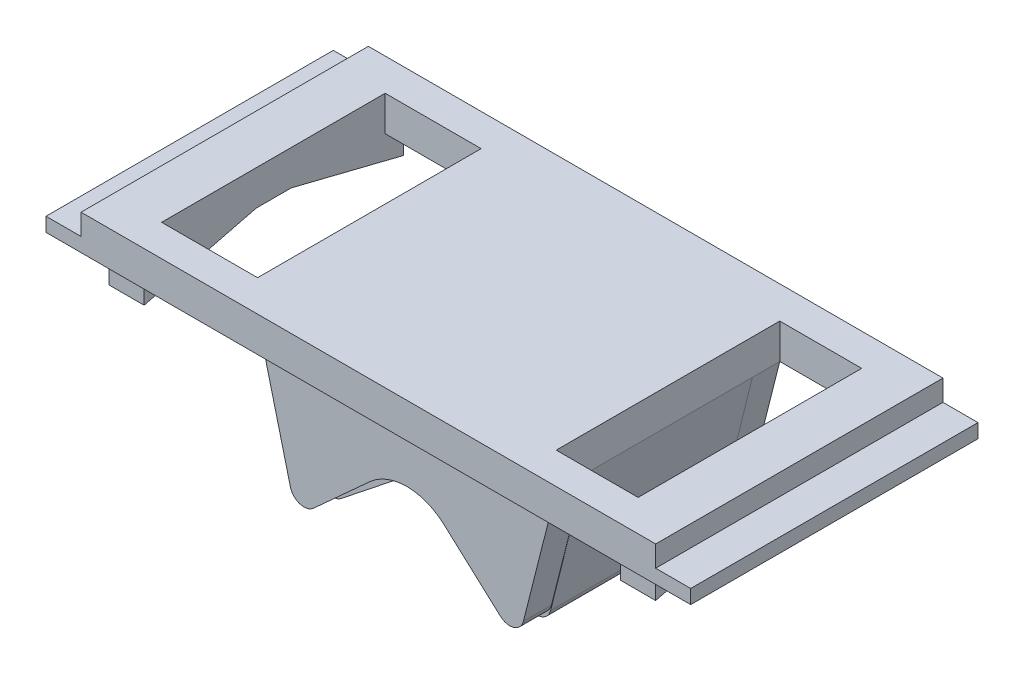
SolidWorks part; units mm, degrees
ref_plane "Спереди" through (0, 0, 0) normal (0, 0, 1) x (1, 0, 0)
ref_plane "Сверху" through (0, 0, 0) normal (0, 1, 0) x (1, 0, 0)
ref_plane "Справа" through (0, 0, 0) normal (1, 0, 0) x (0, 0, -1)
ref_plane "Плоскость4" through (0, 102.0014, 0) normal (0, 1, 0) x (1, 0, 0)
sketch "Эскиз1" plane through (0, 102.0014, 0) normal (0, 1, 0) x (1, 0, 0)
  line L0 (30.7418, -74.5527) -> (106.2994, -74.5527)
  line L1 (106.2994, -74.5527) -> (106.2994, -70.6514)
  line L2 (106.2994, -70.6514) -> (30.7418, -70.6514)
  line L3 (30.7418, -68.0527) -> (30.7418, -105.0527) construction
  line L4 (30.7418, -70.6514) -> (30.7418, -74.5527)
  line L5 (30.7418, -74.5527) -> (30.7418, -98.5527)
  line L6 (30.7418, -98.5527) -> (106.2994, -98.5527)
  line L7 (106.2994, -98.5527) -> (106.2994, -102.5527)
  line L8 (106.2994, -102.5527) -> (30.7418, -102.5527)
  line L9 (-55, -102.5527) -> (55, -102.5527) construction
  line L10 (30.7418, -98.5527) -> (30.7418, -102.5527) construction
  line L11 (30.7418, -102.5527) -> (30.7418, -98.5527)
  line L12 (106.2994, -74.5527) -> (106.2994, -98.5527)
  line L13 (30.7418, -102.5527) -> (30.7418, -105.0527)
  line L14 (76.9629, -105.0527) -> (60.5207, -105.0527) construction
  line L15 (30.7418, -105.0527) -> (106.2994, -105.0527)
  line L16 (-3.85, -105.0527) -> (3.85, -105.0527) construction
  line L17 (106.2994, -105.0527) -> (106.2994, -102.5527)
  line L18 (30.7418, -71.464) -> (30.6074, -68.5533)
  line L19 (30.6074, -68.5533) -> (106.2994, -68.5533)
  line L20 (106.2994, -68.5533) -> (106.2994, -70.6514)
extrude "Бобышка-Вытянуть1" add sketch "Эскиз1" against normal blind 25 contours L2 L4 L0 L1 | L11 L8 L7 L6 region at (68.5206, 102.0014, 72.602) region at (68.5206, 102.0014, 100.5527)
ref_plane "Плоскость5" through (0, 0, 102.5527) normal (0, 0, 1) x (1, 0, 0)
sketch "Эскиз2" plane through (0, 0, 102.5527) normal (0, 0, 1) x (1, 0, 0)
  line L14 (63.5103, 89.8509) -> (52.9371, 80.2581)
  line L15 (30.8, 102.0014) -> (-30.8, 102.0014) construction
  line L27 (47.4349, 102.0014) -> (30.7418, 102.0014)
  line L32 (106.2994, 102.0014) -> (90.0519, 102.0014)
  line L34 (73.9733, 89.8509) -> (84.5476, 80.2629)
  line L38 (84.5476, 80.2629) -> (90.0519, 102.0014)
  line L39 (51.8381, 79.4721) -> (54.0362, 81.0441) construction
  line L40 (52.9371, 80.2581) -> (47.4349, 102.0014)
  line L41 (30.7418, 102.0014) -> (30.7418, 77.0014)
  line L42 (30.7418, 77.0014) -> (106.2994, 77.0014)
  line L43 (106.2994, 77.0014) -> (106.2994, 102.0014)
  arc A10 (63.5103, 89.8509) -> (73.9733, 89.8509) centre (68.7418, 84.0014) cw
extrude "Вырез-Вытянуть15" cut sketch "Эскиз2" against normal blind 32
extrude "Бобышка-Вытянуть5" add sketch "Эскиз1<6>" against normal blind 25 contours L12 L0 L5 L6 region at (68.5206, 102.0014, 86.5527)
sketch "Эскиз1<6>" plane through (0, 102.0014, 0) normal (0, 1, 0) x (1, 0, 0) same geometry as "Эскиз1"
ref_plane "Плоскость7" through (0, 0, 110.0527) normal (0, 0, 1) x (1, 0, 0)
sketch "Эскиз3" plane through (0, 0, 110.0527) normal (0, 0, 1) x (1, 0, 0)
  line L4 (47.4315, 102.0014) -> (52.9371, 79.7482)
  line L5 (30.8, 102.0014) -> (-30.8, 102.0014) construction
  line L6 (90.0519, 102.0014) -> (84.4899, 79.7482)
  line L7 (90.0519, 102.0014) -> (84.5476, 80.2629) construction
  line L8 (72.7967, 89.0816) -> (84.4899, 79.7482)
  line L9 (64.6869, 89.0816) -> (52.9371, 79.7482)
  line L10 (47.4315, 102.0014) -> (30.7338, 102.0014)
  line L11 (30.7338, 102.0014) -> (30.7418, 77.0014)
  line L12 (30.7418, 77.0014) -> (106.2994, 77.0014)
  line L13 (106.2994, 77.0014) -> (106.2994, 102.0014)
  line L14 (106.2994, 77.0014) -> (106.2994, 102.0014) construction
  line L15 (106.2994, 102.0014) -> (90.0519, 102.0014)
  circle A0 centre (68.7418, 84.0014) radius 6.5
  circle A4 centre (93.7418, 80.1014) radius 6.0476
extrude "Вырез-Вытянуть16" cut sketch "Эскиз3" against normal through all both and the other way through all contours A4 L12 L13 L15 L6 L8 A0 L9 L4 L10 L11 | A0 region at (49.4117, 90.6837, 110.0527) region at (68.7418, 84.0014, 110.0527)
fillet "Скругление2" radius 2 4 edges at (52.9371, 80.2581, 100.5527) (52.9371, 80.2581, 72.602) (84.5476, 80.2629, 100.5527) (84.5476, 80.2629, 72.602)
fillet "Скругление3" radius 2 2 edges at (84.4899, 79.7482, 86.5527) (52.9371, 79.7482, 86.5527)
ref_plane "Плоскость8" through (28.7418, 0, 0) normal (1, 0, 0) x (0, 0, -1)
sketch "Эскиз4" plane through (28.7418, 0, 0) normal (1, 0, 0) x (0, 0, -1)
  line L0 (-105.0527, 102.0014) -> (-105.0527, 98.0014)
  line L1 (-105.0527, 84.0014) -> (-105.0527, 102.0014) construction
  line L2 (-105.0527, 102.0014) -> (-89.0527, 102.0014)
  line L3 (-105.0527, 102.0014) -> (-68.0527, 102.0014) construction
  line L4 (-89.0527, 102.0014) -> (-105.0527, 98.0014)
  line L5 (-68.0527, 102.0014) -> (-68.0527, 98.0014)
  line L6 (-68.0527, 84.0014) -> (-68.0527, 102.0014) construction
  line L7 (-68.0527, 102.0014) -> (-84.0527, 102.0014)
  line L8 (-84.0527, 102.0014) -> (-68.0527, 98.0014)
extrude "Бобышка-Вытянуть6" add sketch "Эскиз4" along normal blind 5 separate body
ref_plane "Плоскость9" through (106.7418, 0, 0) normal (-1, 0, 0) x (0, 0, 1)
sketch "Эскиз5" plane through (106.7418, 0, 0) normal (-1, 0, 0) x (0, 0, 1)
  line L0 (105.0527, 102.0014) -> (105.0527, 98.0014)
  line L1 (105.0527, 102.0014) -> (105.0527, 83.2858) construction
  line L2 (105.0527, 102.0014) -> (89.0527, 102.0014)
  line L3 (105.0527, 102.0014) -> (68.0527, 102.0014) construction
  line L4 (68.0527, 102.0014) -> (84.0527, 102.0014)
  line L5 (68.0527, 102.0014) -> (68.0527, 98.0014)
  line L6 (68.0527, 102.0014) -> (68.0527, 83.2896) construction
  line L7 (68.0527, 98.0014) -> (84.0527, 102.0014)
  line L8 (105.0527, 98.0014) -> (89.0527, 102.0014)
extrude "Бобышка-Вытянуть7" add sketch "Эскиз5" along normal blind 5 separate body
ref_plane "Плоскость10" through (0, 102.0014, 0) normal (0, 1, 0) x (1, 0, 0)
sketch "Эскиз6" plane through (0, 102.0014, 0) normal (0, 1, 0) x (1, 0, 0)
  line L0 (26.7418, -107.0527) -> (108.7418, -107.0527)
  line L6 (108.7418, -104.0527) -> (108.7418, -110.0527) construction
  line L10 (108.7418, -107.0527) -> (108.7418, -66.0527)
  line L11 (108.7418, -69.0527) -> (108.7418, -64.0527) construction
  line L13 (26.7418, -107.0527) -> (26.7418, -66.0527)
  line L14 (26.7418, -66.0527) -> (108.7418, -66.0527)
  line L15 (-13.75, -102.5527) -> (13.75, -102.5527) construction
  line L16 (90.0519, -98.5527) -> (90.0519, -102.5527) construction
  line L17 (101.7418, -105.0527) -> (101.7418, -89.0527) construction
  line L18 (98.1534, -102.5527) -> (106.2994, -102.5527) construction
  line L20 (33.7418, -89.0527) -> (33.7418, -105.0527) construction
  line L21 (-55, -102.5527) -> (55, -102.5527) construction
  line L23 (33.7418, -102.5527) -> (47.4349, -102.5527)
  line L24 (33.7418, -102.5527) -> (33.7418, -70.6514)
  line L25 (33.7418, -70.6514) -> (47.4349, -70.6514)
  line L26 (47.4349, -102.5527) -> (47.4349, -70.6514)
  line L27 (101.7418, -102.5527) -> (90.0519, -102.5527)
  line L28 (101.7418, -102.5527) -> (101.7418, -70.6514)
  line L29 (101.7418, -70.6514) -> (90.0519, -70.6514)
  line L30 (90.0519, -102.5527) -> (90.0519, -70.6514)
extrude "Бобышка-Вытянуть8" add sketch "Эскиз6" along normal blind 5
sketch "Эскиз7" plane through (0, 102.0014, 0) normal (0, 1, 0) x (1, 0, 0)
  line L0 (26.7418, -66.0527) -> (21.7418, -66.0527)
  line L1 (26.7418, -107.0527) -> (21.7418, -107.0527)
  line L2 (21.7418, -107.0527) -> (21.7418, -66.0527)
  line L3 (26.7418, -66.0527) -> (26.7418, -107.0527)
  line L4 (108.7418, -66.0527) -> (113.7418, -66.0527)
  line L5 (108.7418, -107.0527) -> (113.7418, -107.0527)
  line L6 (113.7418, -107.0527) -> (113.7418, -66.0527)
  line L7 (108.7418, -66.0527) -> (108.7418, -107.0527)
extrude "Бобышка-Вытянуть9" add sketch "Эскиз7" along normal blind 2
extrude "Вырез-Вытянуть17" cut sketch "Эскиз3<3>" against normal through all both and the other way through all contours L12 A4 region at (93.7418, 81.1026, 110.0527)
sketch "Эскиз3<3>" plane through (0, 0, 110.0527) normal (0, 0, 1) x (1, 0, 0) same geometry as "Эскиз3"
